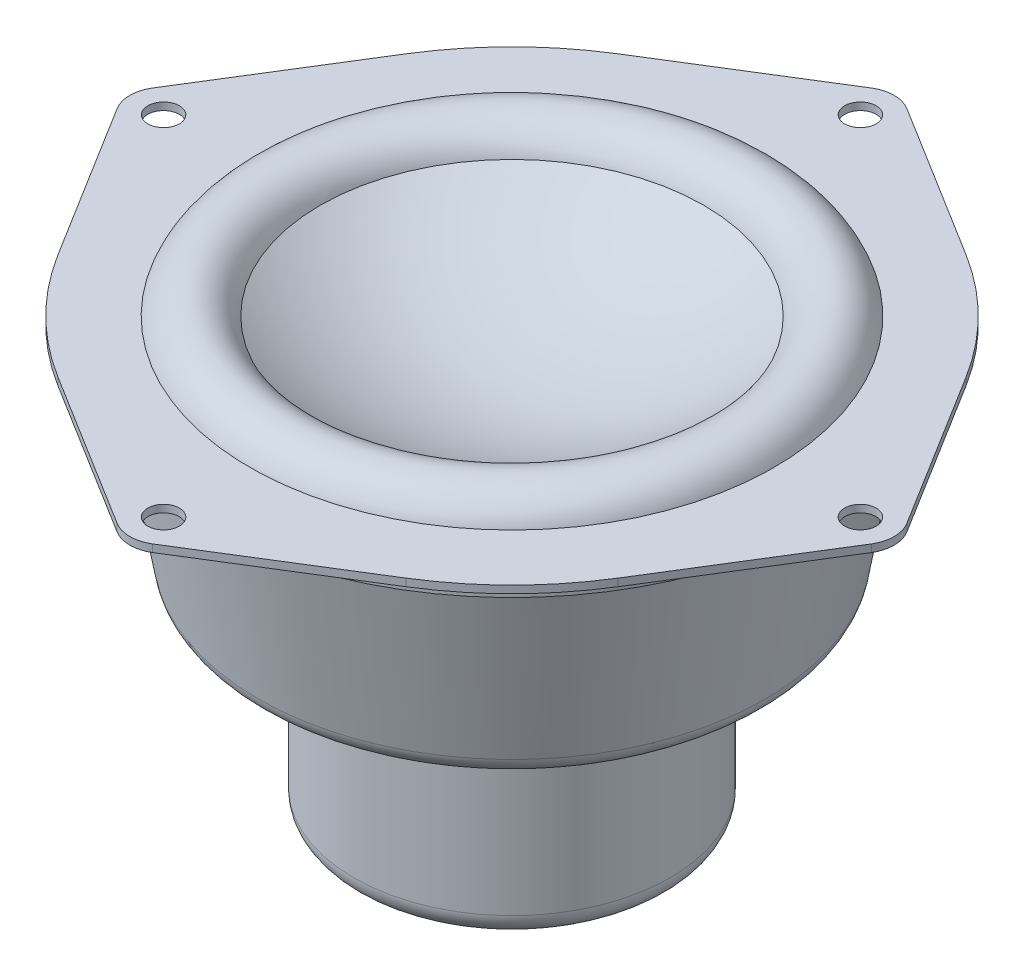
SolidWorks part; units mm, degrees
ref_plane "Front Plane" through (0, 0, 0) normal (0, 0, 1) x (1, 0, 0)
ref_plane "Top Plane" through (0, 0, 0) normal (0, 1, 0) x (1, 0, 0)
ref_plane "Right Plane" through (0, 0, 0) normal (1, 0, 0) x (0, 0, -1)
sketch "Sketch1" plane through (0, 0, 0) normal (0, 1, 0) x (1, 0, 0)
  circle A0 centre (0, 0) radius 21.1
  dimension "D1" = 42.2
extrude "Boss-Extrude1" add sketch "Sketch1" along normal blind 27.6 contours A0
sketch "Sketch2" plane through (0, 27.6, 0) normal (0, 1, 0) x (1, 0, 0)
  circle A0 centre (0, 0) radius 38.25
  dimension "D1" = 76.5
extrude "Boss-Extrude2" add sketch "Sketch2" along normal offset from surface (27.3 mm away) 54.9 up to face at (0, 0, 21.1)
sketch "Sketch3" plane through (0, 54.9, 0) normal (0, 1, 0) x (1, 0, 0)
  circle A0 centre (0, 0) radius 42.5
  dimension "D1" = 85
extrude "Boss-Extrude3" add sketch "Sketch3" along normal offset from surface (1.5 mm away) 56.4 up to face at (0, 0, 21.1)
sketch "Sketch4" plane through (0, 56.4, 0) normal (0, 1, 0) x (1, 0, 0)
  line L0 (-23.2166, 37.3763) -> (-2.3744, 50.3226)
  line L1 (2.3744, 50.3226) -> (23.2166, 37.3763)
  arc A0 (-23.2166, 37.3763) -> (23.2166, 37.3763) centre (0, 0) ccw
  arc A1 (-2.3744, 50.3226) -> (2.3744, 50.3226) centre (0, 46.5) cw
  circle A2 centre (0, 46.5) radius 2.1
  point P7 (0, 0)
  point P9 (0, 0)
  dimension "D1" = 46.5
  dimension "D2" = 88
  dimension "D3" = 4.2
  dimension "D4" = 4.5
extrude "Boss-Extrude4" add sketch "Sketch4" along normal blind 1
pattern_circular "CirPattern1" count 4 over 360 about axis through (0, 217.9873, 0) along (0, -1, 0) of "Boss-Extrude4" reverse direction yes
draft "Draft1" type of draft neutral plane draft angle 10 faces to draft 1 face at (0, 27.6, 38.25) neutral plane through (0, 54.9, 0) neutral plane normal (0, -1, 0) parameters "D1"=10
fillet "Fillet1" radius 3 1 edges at (0, 0, 21.1)
fillet "Fillet2" radius 3 1 edges at (0, 27.6, 33.4363)
sketch "Sketch6" plane through (0, 0, 0) normal (1, 0, 0) x (0, 0, -1)
  line L0 (0, 49.4) -> (0, 0) construction
  line L1 (0, 49.4) -> (-17.2855, 49.4) construction
  line L2 (35, 57.4) -> (39.6803, 44.5411) construction
  line L4 (37.3763, 57.4) -> (23.2166, 57.4) construction
  line L5 (37.3763, 57.4) -> (50.3226, 57.4) construction
  line L6 (2.3744, 57.4) -> (23.2166, 57.4) construction
  line L7 (2.3744, 57.4) -> (-2.3744, 57.4) construction
  line L8 (37.3763, 57.4) -> (50.3226, 57.4)
  line L9 (37.3763, 57.4) -> (23.2166, 57.4)
  line L10 (2.3744, 57.4) -> (23.2166, 57.4)
  line L11 (2.3744, 57.4) -> (0, 57.4)
  line L12 (0, 49.4) -> (0, 57.4)
  arc A0 (0, 49.4) -> (25.5999, 57.3913) centre (0, 94.4) ccw
  arc A1 (25.5999, 57.3913) -> (35, 57.4) centre (30.3015, 55.6899) cw
  point P8 (26.6089, 59.061)
  point P10 (26.0647, 58.3449)
  dimension "D1" = 5
  dimension "D4" = 45
  dimension "D2" = 70
  dimension "D3" = 20
  dimension "D5" = 8
revolve "Cut-Revolve1" cut sketch "Sketch6" angle 360 about L12 region at (0, 54.1743, -9.7297)
revolve "Revolve1" add sketch "Sketch6<4>" angle 360 about L12 region at (0, 58.762, -30.3015)
sketch "Sketch6<4>" plane through (0, 0, 0) normal (1, 0, 0) x (0, 0, -1) same geometry as "Sketch6"
